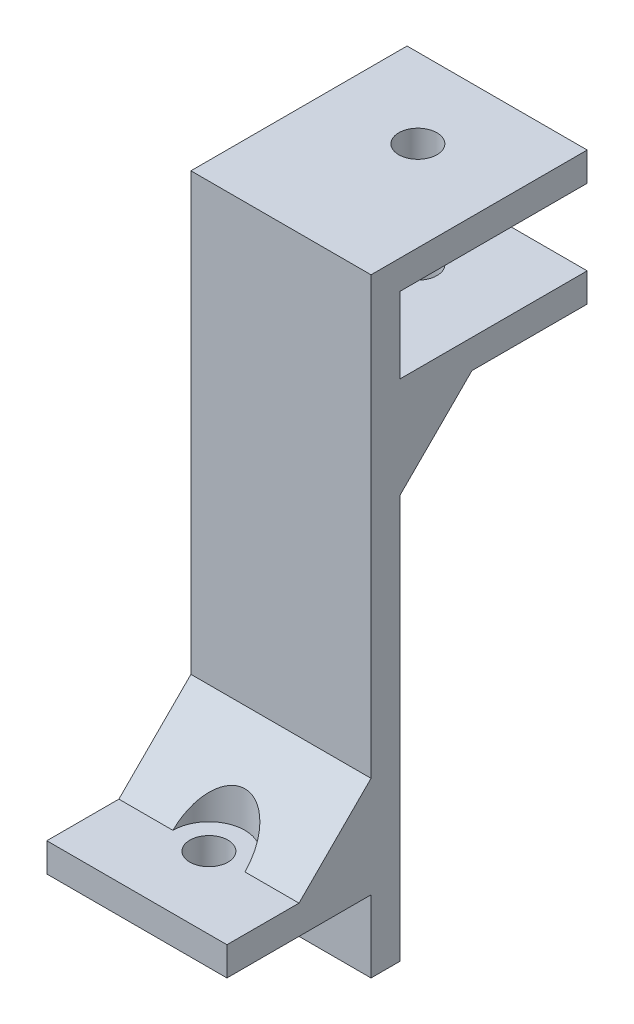
SolidWorks part; units mm, degrees
ref_plane "Front Plane" through (0, 0, 0) normal (0, 0, 1) x (1, 0, 0)
ref_plane "Top Plane" through (0, 0, 0) normal (0, 1, 0) x (1, 0, 0)
ref_plane "Right Plane" through (0, 0, 0) normal (1, 0, 0) x (0, 0, -1)
sketch "Sketch1" plane through (0, 0, 0) normal (1, 0, 0) x (0, 0, -1)
  line L0 (0, 0) -> (0, 10)
  line L1 (4, 70) -> (30, 70)
  line L7 (0, 84.525) -> (30, 84.525)
  line L8 (30, 84.525) -> (30, 80.525)
  line L9 (30, 80.525) -> (4, 80.525)
  line L10 (4, 80.525) -> (4, 70)
  line L11 (0, 14) -> (-20, 14)
  line L12 (-20, 14) -> (-20, 10)
  line L13 (-20, 10) -> (0, 10)
  line L14 (0, 14) -> (0, 84.525)
  line L15 (30, 70) -> (30, 66)
  line L16 (30, 66) -> (4, 66)
  line L17 (4, 66) -> (4, 0)
  line L18 (4, 0) -> (0, 0)
  dimension "D1" = 20
  dimension "D2" = 30
  dimension "D3" = 4
  dimension "D4" = 4
  dimension "D5" = 10.525
  dimension "D6" = 4
  dimension "D7" = 60
  dimension "D8" = 10
  dimension "D9" = 4
  dimension "D10" = 4
extrude "Boss-Extrude1" add sketch "Sketch1" along normal blind 25
sketch "Sketch2" plane through (0, 14, 0) normal (0, 1, 0) x (1, 0, 0)
  line L0 (12.5, 0) -> (12.5, -20) construction
  line L1 (25, 0) -> (0, 0) construction
  line L2 (25, -20) -> (0, -20) construction
  circle A0 centre (12.5, -10) radius 2.65
  dimension "D1" = 5.3
  dimension "D2" = 10
extrude "Cut-Extrude1" cut sketch "Sketch2" against normal blind 6 and the other way blind 6
sketch "Sketch3" plane through (0, 84.525, 0) normal (0, 1, 0) x (1, 0, 0)
  line L0 (12.5, 30) -> (12.5, 0) construction
  line L1 (25, 30) -> (0, 30) construction
  line L2 (25, 0) -> (0, 0) construction
  circle A0 centre (12.5, 19) radius 2.65
  dimension "D1" = 5.3
  dimension "D2" = 19
extrude "Cut-Extrude2" cut sketch "Sketch3" against normal through all
chamfer "Chamfer1" distance 10 angle 45 1 edges at (12.5, 14, 0)
sketch "Sketch4" plane through (0, 14, 0) normal (0, 1, 0) x (1, 0, 0)
  circle A0 centre (12.5, -10) radius 5
  dimension "D1" = 10
extrude "Cut-Extrude4" cut sketch "Sketch4" along normal blind 6
chamfer "Chamfer2" distance 10 angle 45 1 edges at (12.5, 66, -4)
